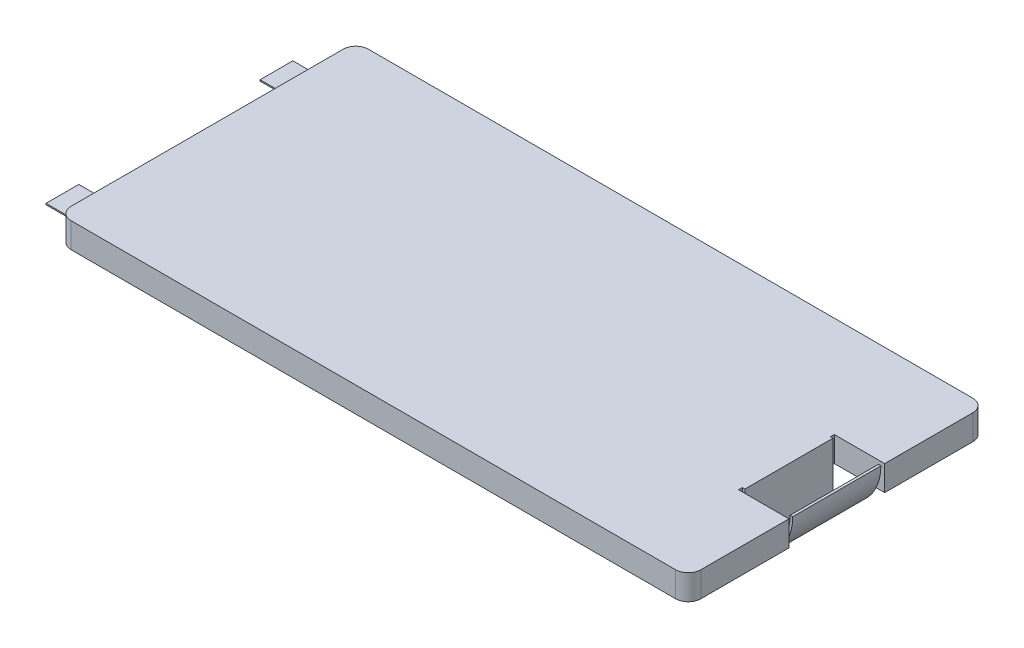
SolidWorks part; units mm, degrees
material "PVB"
ref_plane "Front Plane" through (0, 0, 0) normal (0, 0, 1) x (1, 0, 0)
ref_plane "Top Plane" through (0, 0, 0) normal (0, 1, 0) x (1, 0, 0)
ref_plane "Right Plane" through (0, 0, 0) normal (1, 0, 0) x (0, 0, -1)
ref_axis "X-axis" through (-88.99, 0, 0) along (1, 0, 0)
ref_axis "Y-axis" through (0, 55, 0) along (0, -1, 0)
ref_axis "Z-axis" through (0, 0, -88.99) along (0, 0, 1)
sketch "Sketch1" plane through (0, 0, 0) normal (0, 1, 0) x (1, 0, 0)
  line L1 (-31.75, 14.986) -> (31.75, 14.986)
  line L2 (-31.75, 14.986) -> (-31.75, -14.986)
  line L3 (-31.75, -14.986) -> (31.75, -14.986)
  line L4 (31.75, 14.986) -> (31.75, -14.986)
  line L5 (-31.75, 14.986) -> (31.75, -14.986) construction
  line L6 (-31.75, -14.986) -> (31.75, 14.986) construction
  point P0 (0, 0)
  dimension "D1" = 63.5
  dimension "D2" = 29.972
extrude "Boss-Extrude1" add sketch "Sketch1" along normal blind 2.54
fillet "Fillet1" radius 1.27 4 edges at (-31.75, 1.27, -14.986) (-31.75, 1.27, 14.986) (31.75, 1.27, -14.986) (31.75, 1.27, 14.986)
sketch "Sketch2" plane through (0, 2.54, 0) normal (0, 1, 0) x (1, 0, 0)
  line L0 (31.75, -13.716) -> (31.75, 13.716) construction
  line L1 (36.83, 4.826) -> (26.67, 4.826)
  line L2 (36.83, 4.826) -> (36.83, -4.826)
  line L3 (36.83, -4.826) -> (26.67, -4.826)
  line L4 (26.67, 4.826) -> (26.67, -4.826)
  line L5 (36.83, 4.826) -> (26.67, -4.826) construction
  line L6 (36.83, -4.826) -> (26.67, 4.826) construction
  line L7 (30.48, 14.986) -> (-30.48, 14.986) construction
  point P0 (31.75, 0)
  dimension "D1" = 10.16
  dimension "D2" = 5.08
extrude "Cut-Extrude1" cut sketch "Sketch2" against normal through all
sketch "Sketch3" plane through (0, 0, 0) normal (0, -1, 0) x (1, 0, 0)
  line L0 (26.67, -4.826) -> (26.67, 4.826) construction
  line L1 (29.0566, 3.556) -> (24.2834, 3.556)
  line L2 (29.0566, 3.556) -> (29.0566, -3.556)
  line L3 (29.0566, -3.556) -> (24.2834, -3.556)
  line L4 (24.2834, 3.556) -> (24.2834, -3.556)
  line L5 (29.0566, 3.556) -> (24.2834, -3.556) construction
  line L6 (29.0566, -3.556) -> (24.2834, 3.556) construction
  line L7 (31.75, -4.826) -> (26.67, -4.826) construction
  point P0 (26.67, 0)
  dimension "D1" = 1.27
extrude "Boss-Extrude2" add sketch "Sketch3" along normal blind 2.54 draft 31
sketch "Sketch4" plane through (0, 0, 0) normal (0, 1, 0) x (1, 0, 0)
  line L0 (26.67, 3.556) -> (29.0566, 3.556)
  line L1 (29.0566, 3.556) -> (29.0566, -3.556)
  line L2 (29.0566, -3.556) -> (26.67, -3.556)
  line L3 (26.67, -3.556) -> (26.67, 3.556)
extrude "Cut-Extrude2" cut sketch "Sketch4" against normal through all
sketch "Sketch10" plane through (0, 0, 0) normal (0, 0, 1) x (1, 0, 0)
  line L0 (26.67, 2.54) -> (26.67, -2.54)
  line L1 (26.924, 2.54) -> (26.924, -2.2793)
  line L2 (26.67, 2.54) -> (26.924, 2.54)
  line L3 (31.496, 2.54) -> (31.75, 2.54)
  arc A0 (26.67, -2.54) -> (31.75, 2.54) centre (26.67, 2.54) ccw
  arc A1 (26.924, -2.2793) -> (31.496, 2.54) centre (26.67, 2.54) ccw
  dimension "D1" = 0.254
extrude "Boss-Extrude4" add sketch "Sketch10" along normal mid plane 8.89
sketch "Sketch11" plane through (-31.75, 0, 0) normal (-1, 0, 0) x (0, 0, 1)
  line L0 (-13.716, 0) -> (13.716, 0) construction
  line L1 (9.144, 0) -> (12.446, 0)
  line L2 (9.144, 0) -> (9.144, 0.254)
  line L3 (9.144, 0.254) -> (12.446, 0.254)
  line L4 (12.446, 0) -> (12.446, 0.254)
  line L5 (-14.986, 0) -> (-14.986, 2.54) construction
  line L6 (-12.446, 0) -> (-9.144, 0)
  line L7 (-12.446, 0) -> (-12.446, 0.254)
  line L8 (-12.446, 0.254) -> (-9.144, 0.254)
  line L9 (-9.144, 0) -> (-9.144, 0.254)
  line L10 (14.986, 2.54) -> (14.986, 0) construction
  dimension "D1" = 3.302
  dimension "D2" = 2.54
  dimension "D3" = 2.54
  dimension "D4" = 0.254
extrude "Boss-Extrude5" add sketch "Sketch11" along normal blind 3.81 separate body
sketch "Sketch12" plane through (-31.75, 0, 0) normal (-1, 0, 0) x (0, 0, 1)
  line L0 (-9.144, 0) -> (-9.144, 0.254) construction
  line L1 (-12.446, 0) -> (-9.144, 0)
  line L2 (-12.446, 0) -> (-12.446, 0.127)
  line L3 (-12.446, 0.127) -> (-9.144, 0.127)
  line L4 (-9.144, 0) -> (-9.144, 0.127)
  line L5 (9.144, 0.254) -> (9.144, 0) construction
  line L6 (12.446, 0) -> (9.144, 0)
  line L7 (12.446, 0) -> (12.446, 0.127)
  line L8 (12.446, 0.127) -> (9.144, 0.127)
  line L9 (9.144, 0) -> (9.144, 0.127)
extrude "Cut-Extrude3" cut sketch "Sketch12" along normal through all
